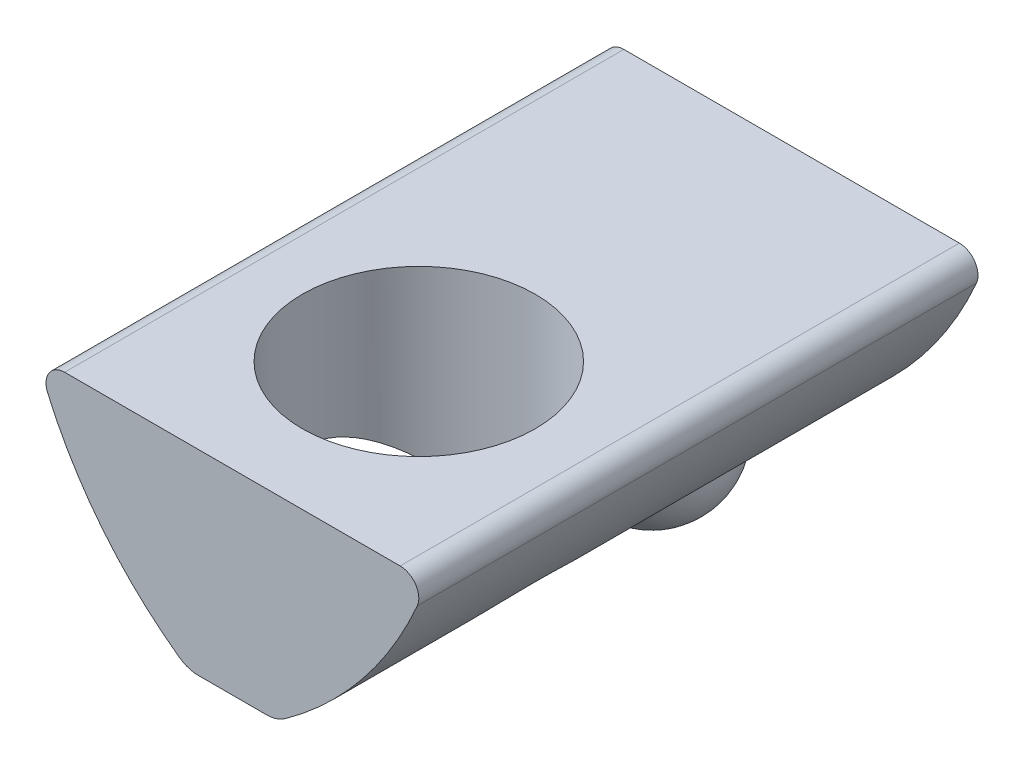
SolidWorks part; units mm, degrees
material "Plain Carbon Steel"
ref_plane "Front Plane" through (0, 0, 0) normal (0, 0, 1) x (1, 0, 0)
ref_plane "Top Plane" through (0, 0, 0) normal (0, 1, 0) x (1, 0, 0)
ref_plane "Right Plane" through (0, 0, 0) normal (1, 0, 0) x (0, 0, -1)
sketch "Sketch1" plane through (0, 0, 0) normal (0, 1, 0) x (1, 0, 0)
  circle A0 centre (0, 0) radius 2.5
  point P2 (2.5, 0)
  point P3 (-2.5, 0)
  dimension "D1" = 5
extrude "Boss-Extrude1" add sketch "Sketch1" against normal blind 8
sketch "Sketch2" plane through (0, -8, 0) normal (0, -1, 0) x (1, 0, 0)
  circle A1 centre (0, 0) radius 2.5
  circle A2 centre (0, 0) radius 2.5
  point P0 (0, -2.5)
  dimension "D1" = 0
curve "Helix/Spiral1" pitch 0.8 height 8.8 turns 11
sketch "Sketch3" plane through (0, 0, 0) normal (1, 0, 0) x (0, 0, -1)
  line L0 (2.5866, -7.95) -> (1.8938, -8.35) construction
  line L1 (1.8938, -8.35) -> (2.5866, -8.75) construction
  line L2 (2.5866, -8.75) -> (2.5866, -7.95) construction
  line L3 (1.9804, -8.3) -> (1.9804, -8.4) construction
  line L4 (2.5, -8) -> (2.5, -8.7) construction
  line L5 (1.8938, -8.35) -> (1.9804, -8.35) construction
  line L6 (2.5, -8.35) -> (2.5866, -8.35) construction
  line L8 (1.8938, -8.35) -> (-2.5, -8.35) construction
  line L9 (1.9804, -8.3) -> (2.5433, -7.975)
  line L10 (1.9804, -8.3) -> (1.9804, -8.4)
  line L11 (1.9804, -8.4) -> (2.5433, -8.725)
  line L12 (2.5433, -8.725) -> (2.5433, -7.975)
  line L14 (-2.5, -8.35) -> (-2.5, -7.55) construction
  line L15 (-2.5, -7.55) -> (-2.5, -6.75) construction
  line L16 (-2.5, -6.75) -> (-2.5, -5.95) construction
  line L17 (-2.5, -5.95) -> (-2.5, -5.15) construction
  line L18 (-2.5, 0) -> (-2.5, -8) construction
  point P15 (2.5433, -8.35)
  dimension "D1" = 0.8
  dimension "D2" = 0.1
sweep "Cut-Sweep1" cut profiles "Sketch3" path "Helix/Spiral1" align with end faces yes
sketch "SketchZ" plane through (0, 0, 0) normal (0, 0, 1) x (1, 0, 0)
  line L0 (0, -8.35) -> (0, -7.95) construction
  line L1 (0, -8.15) -> (2.5, -8.15) construction
  line L2 (2.5, -8.15) -> (2.5, -7.35) construction
  line L3 (0, -8.35) -> (0, -7.55) construction
sketch "Sketch4" plane through (0, -8, 0) normal (0, -1, 0) x (1, 0, 0)
  circle A0 centre (0, 0) radius 1.8938
extrude "Cut-Extrude1" cut sketch "Sketch4" against normal blind 0.8 draft 45 flip side to cut
sketch "Sketch5" plane through (0, 0, 0) normal (0, 0, 1) x (1, 0, 0)
  line L0 (0, 2.8) -> (0, 0)
  line L1 (0, 0) -> (-5.8, 0) construction
  line L2 (0, 2.8) -> (-2.5, 2.8)
  line L3 (-5.8, 0) -> (-5.8, 0.7) construction
  line L4 (-5.8, 0.7) -> (-4.75, 0.7) construction
  line L5 (0, 0) -> (0, -13.9857) construction
  line L6 (-4.75, 0.7) -> (-4.75, 0)
  line L7 (-4.75, 0) -> (0, 0)
  arc A0 (-4.75, 0.7) -> (-2.5, 2.8) centre (0, -2.1339) cw
  dimension "D1" = 9.5
  dimension "D2" = 5.8
  dimension "D3" = 2.8
  dimension "D4" = 0.7
revolve "Revolve1" add sketch "Sketch5" angle 360 mid plane about L5
sketch "Sketch6" plane through (0, 2.8, 0) normal (0, 1, 0) x (1, 0, 0)
  line L1 (0, 1.7321) -> (-1.5, 0.866)
  line L2 (-1.5, 0.866) -> (-1.5, -0.866)
  line L3 (-1.5, -0.866) -> (0, -1.7321)
  line L4 (0, -1.7321) -> (1.5, -0.866)
  line L5 (1.5, -0.866) -> (1.5, 0.866)
  line L6 (1.5, 0.866) -> (0, 1.7321)
  circle A0 centre (0, 0) radius 1.5 construction
  dimension "D1" = 3
extrude "Cut-Extrude2" cut sketch "Sketch6" against normal blind 1.8
sketch "Sketch7" plane through (0, 2.8, 0) normal (0, 1, 0) x (1, 0, 0)
  circle A0 centre (0, 0) radius 1.7321
extrude "Cut-Extrude3" cut sketch "Sketch7" against normal blind 1.8 draft 45
sketch "Sketch8" plane through (0, 0, 0) normal (0, 0, 1) x (1, 0, 0)
  line L0 (4, -2) -> (4, -6.2) construction
  line L4 (4, -6.2) -> (-4, -6.2) construction
  line L7 (-4, -2) -> (4, -2) construction
  line L10 (0, 0) -> (0, -2) construction
  line L11 (-4, -6.2) -> (-4, -2) construction
  line L12 (-0.7295, -6.2) -> (0.7295, -6.2)
  line L13 (-3.6, -2) -> (3.6, -2)
  line L18 (0, -2) -> (0, -6.2) construction
  arc A1 (-1.1386, -6.0681) -> (-3.9668, -2.5595) centre (3.8282, 0.8299) cw
  arc A2 (-3.9668, -2.5595) -> (-3.6, -2) centre (-3.6, -2.4) cw
  arc A3 (3.9668, -2.5595) -> (3.6, -2) centre (3.6, -2.4) ccw
  arc A4 (1.1386, -6.0681) -> (3.9668, -2.5595) centre (-3.8282, 0.8299) ccw
  arc A5 (-0.7295, -6.2) -> (-1.1386, -6.0681) centre (-0.7295, -5.5) cw
  arc A6 (0.7295, -6.2) -> (1.1386, -6.0681) centre (0.7295, -5.5) ccw
  point P17 (-0.95, -6.2)
  dimension "D1" = 8
  dimension "D3" = 1.9
  dimension "D4" = 8.5
  dimension "D6" = 0.4
  dimension "D7" = 0.7
  dimension "D2" = 2
  dimension "D5" = 4.2
extrude "Boss-Extrude2" add sketch "Sketch8" against normal blind 12 from offset 4 separate body
sketch "Sketch9" plane through (0, 0, 0) normal (0, 1, 0) x (1, 0, 0)
  line L0 (0, -4) -> (0, 0) construction
  line L1 (0, 0) -> (0, 5) construction
  line L3 (3.6, -4) -> (-3.6, -4) construction
  circle A1 centre (0, 5) radius 1.5 construction
  circle A2 centre (0, 0) radius 2.5
  circle A3 centre (0, 0) radius 2.5
  point P9 (0, 6.5)
  dimension "D3" = 3
  dimension "D1" = 9
  dimension "D2" = 0
extrude "Cut-Extrude4" cut sketch "Sketch9" against normal through all
sketch "Sketch10" plane through (0, 0, 0) normal (1, 0, 0) x (0, 0, -1)
  line L0 (5, -6.2) -> (5, -2.2)
  line L1 (5, -2.2) -> (5, 0) construction
  line L2 (5, -2.2) -> (6.5, -2.2)
  line L3 (6.5, -2.2) -> (6.5, -6.2)
  line L4 (6.5, -6.2) -> (5, -6.2)
  line L5 (8, -6.2) -> (2.3912, -6.2) construction
  dimension "D1" = 4
revolve "Cut-Revolve1" cut sketch "Sketch10" angle 360 about L1
sketch "Sketch11" plane through (0, 0, 0) normal (1, 0, 0) x (0, 0, -1)
  line L0 (5, -6.2) -> (5, -2.2) construction
  line L1 (5, -4.3) -> (5, -7.3)
  line L2 (8, -2) -> (-4, -2) construction
  line L3 (6.5, -2.2) -> (6.5, -6.2) construction
  arc A0 (5, -7.3) -> (5, -4.3) centre (5, -5.8) ccw
  dimension "D1" = 5.3
revolve "Revolve2" add sketch "Sketch11" angle 360 about L1
delete or keep bodies "Body-Delete/Keep 1" type delete bodies bodies 110
equation "\"D3@Helix/Spiral1\" = \"D4@Helix/Spiral1\" + \"D1@Boss-Extrude1\""
equation "\"D1@Sketch3\" = \"D4@Helix/Spiral1\""
equation "\"D2@Sketch3\" = \"D1@Sketch3\" / 8"
equation "\"D1@Cut-Extrude1\" = \"D4@Helix/Spiral1\""
equation "\"D1@Cut-Extrude2\" = \"D1@Sketch6\" * 3/5"
equation "\"D1@Cut-Extrude3\" = \"D1@Cut-Extrude2\""
equation "\"D4@Sketch5\" = \"D3@Sketch5\" * 1/4"
